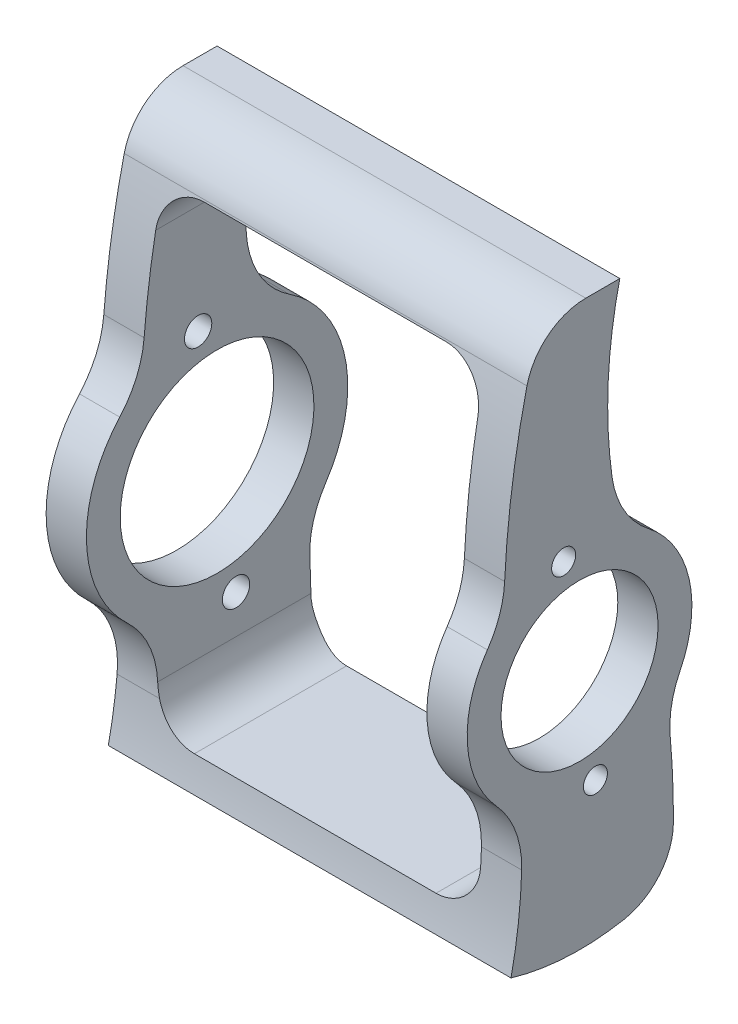
SolidWorks part; units mm, degrees
other "Markup2"
sketch "Sketch9" plane through (31.75, 50.4016, 20.35) normal (0.8402, 0.4575, 0.2911) x (0.3274, 0, -0.9449)
material "AISI 4340 Steel, normalized"
ref_plane "Front Plane" through (0, 0, 0) normal (0, 0, 1) x (1, 0, 0)
ref_plane "Top Plane" through (0, 0, 0) normal (0, 1, 0) x (1, 0, 0)
ref_plane "Right Plane" through (0, 0, 0) normal (1, 0, 0) x (0, 0, -1)
other "Center of Mass"
sketch "Weapon Layout" plane through (0, 0, 0) normal (1, 0, 0) x (0, 0, -1)
  line L0 (-6.35, 50.4016) -> (6.35, 50.4016) construction
  line L1 (-10.8026, -36.5365) -> (14.5626, -35.2071) construction
  line L2 (6.35, 50.4016) -> (-5.4537, 0) construction
  line L3 (6.35, 50.4016) -> (0, 0) construction
  line L4 (0, 0) -> (0, -35.9703) construction
  circle A0 centre (0, 0) radius 14 construction
  circle A1 centre (0, 0) radius 50.8 construction
  circle A2 centre (0, 0) radius 17.175 construction
  circle A3 centre (0, 0) radius 20.35 construction
  arc A4 (-6.35, 50.4016) -> (-20.35, 0) centre (77.3756, 0) ccw construction
  arc A5 (25.0504, -28.707) -> (-25.4024, -28.3959) centre (0, 0) cw construction
  arc A6 (6.35, 50.4016) -> (15.4347, 13.2625) centre (47.4536, 40.7754) ccw construction
  dimension "D1" = 28
  dimension "D2" = 101.6
  dimension "D3" = 3.175
  dimension "D4" = 6.35
  dimension "D5" = 12.7
  dimension "D7" = 6
  dimension "D6" = 12.7
  dimension "D8" = 25.4
  dimension "D9" = 87
sketch "Sketch2" plane through (0, 0, 0) normal (1, 0, 0) x (0, 0, -1)
  line L0 (-6.35, 50.4016) -> (6.35, 50.4016)
  line L1 (-11.3119, -1.6391) -> (0, 0) construction
  line L2 (6.35, 50.4016) -> (-5.4537, 0) construction
  line L3 (-11.6027, 1.0256) -> (-15.24, 50.4016) construction
  arc A0 (-10.8026, -36.5365) -> (14.5626, -35.2071) centre (0, 0) ccw
  arc A1 (-25.4024, -28.3959) -> (25.0504, -28.707) centre (0, 0) ccw construction
  arc A2 (-10.8344, -4.2769) -> (-11.6027, 1.0256) centre (26.3943, 3.8247) cw
  arc A3 (9.8248, 6.4214) -> (11.7322, 0.3423) centre (-25.4469, -7.9841) cw
  arc A4 (-11.6027, 1.0256) -> (-6.35, 50.4016) centre (127.0686, 11.2409) cw
  arc A5 (-10.8344, -4.2769) -> (-10.8026, -36.5365) centre (-85.2917, -20.4799) cw
  arc A6 (6.35, 50.4016) -> (9.8248, 6.4214) centre (76.9988, 33.8561) ccw
  arc A7 (11.7322, 0.3423) -> (14.5626, -35.2071) centre (-112.198, -27.4122) cw
  circle A9 centre (0, 0) radius 11.43 construction
  point P25 (10.9058, 3.4217)
  dimension "D1" = 127
  dimension "D2" = 38.1
  dimension "D3" = 76.2
  dimension "D4" = 38.1
  dimension "D5" = 22.86
  dimension "D6" = 8.89
extrude "Boss-Extrude2" add sketch "Sketch2" along normal mid plane 63.5
sketch "Sketch3" plane through (0, 0, 0) normal (0, 0, 1) x (1, 0, 0)
  line L0 (31.75, 50.4016) -> (-31.75, 50.4016) construction
  line L1 (-25.4, 42.7816) -> (25.4, 42.7816)
  line L2 (-25.4, 42.7816) -> (-25.4, -31.75)
  line L3 (-25.4, -31.75) -> (25.4, -31.75)
  line L4 (25.4, 42.7816) -> (25.4, -31.75)
  line L6 (-31.75, -38.1) -> (31.75, -38.1) construction
  line L7 (-31.75, 50.4016) -> (-31.75, 1.0256) construction
  dimension "D4" = 6.35
  dimension "D1" = 7.62
  dimension "D3" = 6.35
  dimension "D2" = 6.35
extrude "Cut-Extrude1" cut sketch "Sketch3" against normal through all both and the other way through all
fillet "Fillet1" radius 6.35 4 edges at (-25.4, 42.7816, 1.6822) (25.4, 42.7816, 1.6822) (25.4, -31.75, -2.3991) (-25.4, -31.75, -2.3991)
fillet "Fillet3" radius 9.525 2 edges at (0, -35.2071, -14.5626) (0, 50.4016, 6.35)
sketch "Sketch6" plane through (-31.75, 0, 0) normal (-1, 0, 0) x (0, 0, 1)
  circle A0 centre (0, 0) radius 20.604
  dimension "D1" = 41.208
extrude "Boss-Extrude3" add sketch "Sketch6" against normal up to surface (6.35 mm away) up to face at (-25.4, 3.1892, 0.2294)
sketch "Sketch7" plane through (-31.75, 0, 0) normal (-1, 0, 0) x (0, 0, 1)
  circle A0 centre (0, 0) radius 15.27
  arc A1 (9.1181, -18.4766) -> (11.8655, 16.8444) centre (0, 0) ccw construction
  dimension "D1" = 30.54
extrude "Cut-Extrude3" cut sketch "Sketch7" against normal up to next
sketch "Sketch10" plane through (31.75, 0, 0) normal (1, 0, 0) x (0, 0, -1)
  circle A0 centre (0, 0) radius 17.7165
  dimension "D1" = 35.433
extrude "Boss-Extrude4" add sketch "Sketch10" against normal up to surface (6.35 mm away) up to face at (25.4, 3.1892, 0.2294)
sketch "Sketch5" plane through (31.75, 0, 0) normal (1, 0, 0) x (0, 0, -1)
  circle A0 centre (0, 0) radius 12.3825
  circle A1 centre (0, 0) radius 6.35 construction
  dimension "D1" = 12.7
  dimension "D2" = 24.765
extrude "Cut-Extrude2" cut sketch "Sketch5" against normal up to next
fillet "Fillet2" radius 15.24 8 edges at (-28.575, 16.8444, 11.8655) (-28.575, -18.4766, 9.1181) (-28.575, -14.9406, -14.1881) (-28.575, 19.765, -5.8198) (28.575, 16.4593, -6.5548) (28.575, -11.162, -13.7581) (28.575, -15.09, 9.2826) (28.575, 13.0644, 11.9665)
sketch "Sketch11" plane through (31.75, 0, 0) normal (1, 0, 0) x (0, 0, -1)
  circle A0 centre (-2.502, 16.1587) radius 1.8986
  circle A1 centre (-2.502, 16.1587) radius 1.8986 construction
  circle A2 centre (2.502, -16.1587) radius 1.8987
  circle A3 centre (2.502, -16.1587) radius 1.8986 construction
extrude "Cut-Extrude4" cut sketch "Sketch11" against normal up to surface (6.35 mm away) up to face at (25.4, 0, -12.3825)
hole_wizard "#6 Clearance Hole1" positions "Sketch12" profile "Sketch13" hole size "#6" standard "ANSI Inch"
sketch "Sketch12" plane through (-31.75, 0, 0) normal (1, 0, 0) x (0, 0, -1)
  point P0 (-2.9885, 19.3009)
  point P3 (2.9885, -19.3009)
sketch "Sketch13" plane through (-31.75, 19.3009, 2.9885) normal (0, 1, 0) x (0, 0, 1)
  line L0 (0, 0) -> (0, 8.9134)
  line L1 (0, 8.9134) -> (2.1526, 7.62)
  line L2 (2.1526, 7.62) -> (2.1526, 0)
  line L5 (2.1526, 0) -> (0, 0)
  line L10 (0, 8.9134) -> (-2.1527, 7.62) construction
  line L11 (0, -6.35) -> (0, 107.95) construction
  dimension "Hole Dia." = 4.3053
  dimension "Hole Depth" = 7.62
  dimension "Drill Angle" = 118
other "Center of Mass Reference Point1"
equation "\"D1@Weapon Layout\" = 28mm"
equation "\"D1@Sketch6\"=\"bearing OD L\"+.42in+0.1in"
equation "\"D2@Sketch3\"=\"D3@Sketch3\""
equation "\"D1@Sketch7\"=\"bearing OD L\"+0.1in"
equation "\"D2@Sketch5\"=\"bearing OD R\" + .1"
equation "\"D1@Sketch10\"=\"bearing OD R\" + 0.42 + .1"
equation "\"bearing OD R\"= 7 / 8"
equation "\"bearing OD L\"= 28mm"
